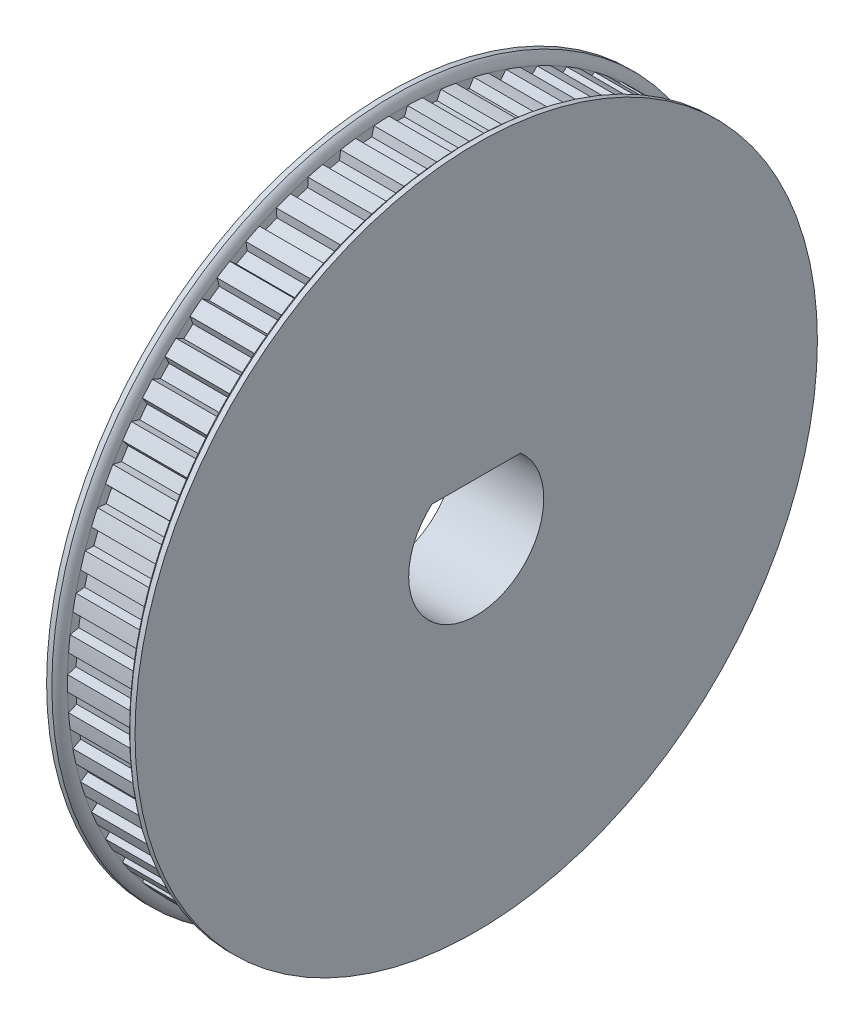
SolidWorks part; units mm, degrees
ref_plane "Front Plane" through (0, 0, 0) normal (0, 0, 1) x (1, 0, 0)
ref_plane "Top Plane" through (0, 0, 0) normal (0, 1, 0) x (1, 0, 0)
ref_plane "Right Plane" through (0, 0, 0) normal (1, 0, 0) x (0, 0, -1)
sketch "Sketch1" plane through (0, 0, 0) normal (1, 0, 0) x (0, 0, -1)
  line L3 (0, 0) -> (0, 50.285) construction
  line L6 (0, 50.285) -> (0, 51.485) construction
  line L7 (-1.325, 51.4679) -> (-0.8916, 50.2771)
  line L8 (1.325, 51.4679) -> (0.8916, 50.2771)
  line L9 (0, -2.2) -> (0, -3.2) construction
  line L10 (0, 51.985) -> (0, 51.485) construction
  line L12 (-0.8916, 50.2771) -> (0.8916, 50.2771)
  line L15 (0, 0) -> (0, -2.2) construction
  circle A0 centre (0, 0) radius 51.985 construction
  circle A1 centre (0, 0) radius 50.285 construction
  arc A7 (1.325, 51.4679) -> (-1.325, 51.4679) centre (0, 0) ccw
  dimension "PD" = 103.97
  dimension "D1" = 40
  dimension "D3" = 0.5
  dimension "D2" = 1.2
  dimension "D4" = 2.65
sketch "Sketch2" plane through (0, 0, 0) normal (0, 0, 1) x (1, 0, 0)
  line L0 (-10.5, 0) -> (10.5, 0) construction
  line L1 (-10.5, 4) -> (10.5, 4) construction
  line L2 (-10.5, 4) -> (-10.5, 19) construction
  line L3 (-2.2, 53) -> (-1.45, 53)
  line L4 (-0.7, 51.485) -> (-2.2, 51.485) construction
  line L5 (9.75, 51.485) -> (9.75, 53) construction
  line L6 (-0.7, 51.485) -> (9, 51.485)
  line L7 (-2.2, 19) -> (-2.2, 4)
  line L8 (9, 51.485) -> (10.5, 51.485) construction
  line L9 (9.75, 53) -> (10.5, 53)
  line L10 (10.5, 53) -> (10.5, 4)
  line L11 (-2.2, 4) -> (10.5, 4)
  line L12 (-6.35, 19) -> (-6.35, 4) construction
  line L13 (-2.2, 53) -> (-2.2, 19)
  line L14 (-2.2, 19) -> (-10.5, 19) construction
  arc A0 (9, 51.485) -> (9.75, 53) centre (10.9052, 51.485) cw
  arc A1 (-0.7, 51.485) -> (-1.45, 53) centre (-2.6052, 51.485) ccw
  point P19 (-0.7, 51.485)
  point P20 (9, 51.485)
  dimension "Bore Size" = 4
  dimension "Overall Width" = 21
  dimension "Inside Width" = 9.7
  dimension "Outside Width" = 12.7
  dimension "Hub Dia" = 19
  dimension "OD" = 106
sketch "Sketch6" plane through (0, 0, 0) normal (0, 0, 1) x (1, 0, 0)
  line L0 (9.75, 53) -> (10.5, 53) construction
  line L1 (-0.7, 51.485) -> (9, 51.485) construction
  line L2 (-2.2, 53) -> (-1.45, 53) construction
  line L3 (-2.2, 53) -> (-2.2, 19) construction
  line L4 (-2.2, 19) -> (-10.5, 19) construction
  line L5 (-10.5, 4) -> (-10.5, 19) construction
  line L6 (-10.5, 4) -> (10.5, 4) construction
  line L7 (10.5, 53) -> (10.5, 4) construction
  line L8 (9.75, 53) -> (10.5, 53)
  line L9 (-0.7, 51.485) -> (9, 51.485)
  line L10 (-2.2, 53) -> (-1.45, 53)
  line L11 (-2.2, 53) -> (-2.2, 19)
  line L12 (-2.2, 19) -> (-10.5, 19)
  line L13 (-10.5, 4) -> (-10.5, 19)
  line L14 (-10.5, 4) -> (10.5, 4)
  line L15 (10.5, 53) -> (10.5, 4)
  line L16 (-2.2, 19) -> (-2.2, 4)
  arc A0 (9.75, 53) -> (9, 51.485) centre (10.9052, 51.485) ccw construction
  arc A1 (-0.7, 51.485) -> (-1.45, 53) centre (-2.6052, 51.485) ccw construction
  arc A2 (9.75, 53) -> (9, 51.485) centre (10.9052, 51.485) ccw
  arc A3 (-0.7, 51.485) -> (-1.45, 53) centre (-2.6052, 51.485) ccw
revolve "Revolve1" add sketch "Sketch6" angle 360 about L14 region at (4.15, 27.8978, 0)
sketch "Sketch3" plane through (0, 0, 0) normal (1, 0, 0) x (0, 0, -1)
  line L2 (-1.325, 51.4679) -> (-0.8916, 50.2771) construction
  line L3 (-0.8916, 50.2771) -> (0.8916, 50.2771) construction
  line L4 (1.325, 51.4679) -> (0.8916, 50.2771) construction
  line L5 (-1.325, 51.4679) -> (-0.8916, 50.2771)
  line L6 (-0.8916, 50.2771) -> (0.8916, 50.2771)
  line L7 (1.325, 51.4679) -> (0.8916, 50.2771)
  arc A1 (1.325, 51.4679) -> (-1.325, 51.4679) centre (0, 0) ccw construction
  arc A2 (1.325, 51.4679) -> (-1.325, 51.4679) centre (0, 0) ccw
extrude "Cut-Extrude1" cut sketch "Sketch3" along normal up to vertex (9 mm away) from vertex up to point (9, 51.485, 0) starting at point (-0.7, 51.485, 0)
pattern_circular "CirPattern1" count 62 over 360 about axis through (-10.5, 4, 0) along (-1, 0, 0) of "Cut-Extrude1"
sketch "Sketch5" plane through (0, 0, 0) normal (0, 0, 1) x (1, 0, 0)
  line L0 (-10.5, 0) -> (10.5, 0) construction
  point P0 (9, 0)
sketch "Sketch8" plane through (-2.2, 0, 0) normal (-1, 0, 0) x (0, 0, 1)
  line L0 (-6.3617, 11.3225) -> (6.3617, 11.3225)
  arc A0 (-6.3617, 11.3225) -> (6.3617, 11.3225) centre (0, 4) ccw
  circle A1 centre (0, 4) radius 49 construction
  dimension "D1" = 19.4
  dimension "D2" = 7.3225
extrude "Cut-Extrude2" cut sketch "Sketch8" against normal through all
equation "\"D3@Sketch1\" = \"ht@Sketch1\" / 2"
equation "\"D2@Sketch1\" = \"hs@Sketch1\" - \"ht@Sketch1\""
